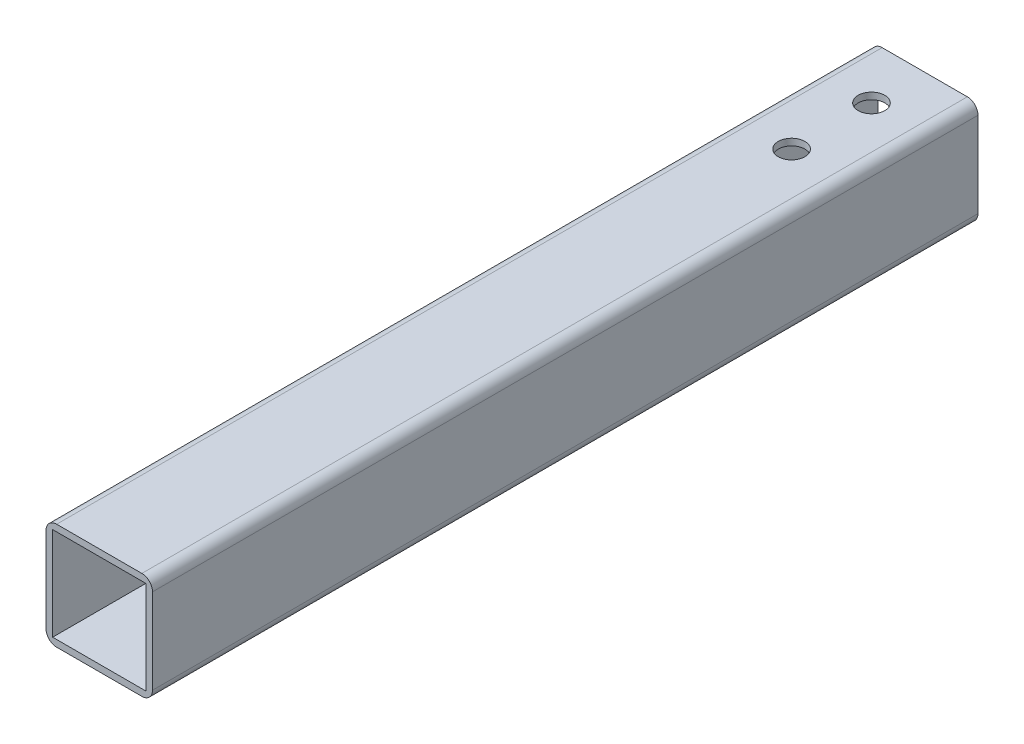
SolidWorks part; units mm, degrees
ref_plane "Front Plane" through (0, 0, 0) normal (0, 0, 1) x (1, 0, 0)
ref_plane "Top Plane" through (0, 0, 0) normal (0, 1, 0) x (1, 0, 0)
ref_plane "Right Plane" through (0, 0, 0) normal (1, 0, 0) x (0, 0, -1)
sketch "Sketch1" plane through (0, 0, 0) normal (0, 0, 1) x (1, 0, 0)
  line L1 (-24.2596, 11.4248) -> (1.1404, 11.4248)
  line L2 (-24.2596, 11.4248) -> (-24.2596, -13.9752)
  line L3 (-24.2596, -13.9752) -> (1.1404, -13.9752)
  line L4 (1.1404, 11.4248) -> (1.1404, -13.9752)
  line L5 (-22.6721, 9.8373) -> (-0.4471, 9.8373)
  line L6 (-22.6721, 9.8373) -> (-22.6721, -12.3877)
  line L7 (-22.6721, -12.3877) -> (-0.4471, -12.3877)
  line L8 (-0.4471, 9.8373) -> (-0.4471, -12.3877)
  dimension "D1" = 25.4
  dimension "D2" = 25.4
  dimension "D3" = 1.5875
  dimension "D4" = 1.5875
  dimension "D5" = 1.5875
  dimension "D6" = 1.5875
extrude "Boss-Extrude1" add sketch "Sketch1" along normal blind 196.85
fillet "Fillet1" radius 2.54 4 edges at (1.1404, -13.9752, 98.425) (-24.2596, -13.9752, 98.425) (-24.2596, 11.4248, 98.425) (1.1404, 11.4248, 98.425)
sketch "Sketch2" plane through (0, 11.4248, 0) normal (0, 1, 0) x (1, 0, 0)
  line L0 (-1.3996, 0) -> (-21.7196, 0) construction
  line L1 (0, 0) -> (0, -59.7417) construction
  line L2 (-11.5596, -12.7) -> (-11.5596, 0) construction
  line L3 (-1.3996, -196.85) -> (-1.3996, 0) construction
  circle A0 centre (-11.5596, -12.7) radius 3.175
  circle A2 centre (-11.5596, -31.75) radius 3.175
  dimension "D1" = 6.35
  dimension "D2" = 12.7
  dimension "D3" = 6.35
  dimension "D6" = 19.05
extrude "Cut-Extrude1" cut sketch "Sketch2" against normal through all
